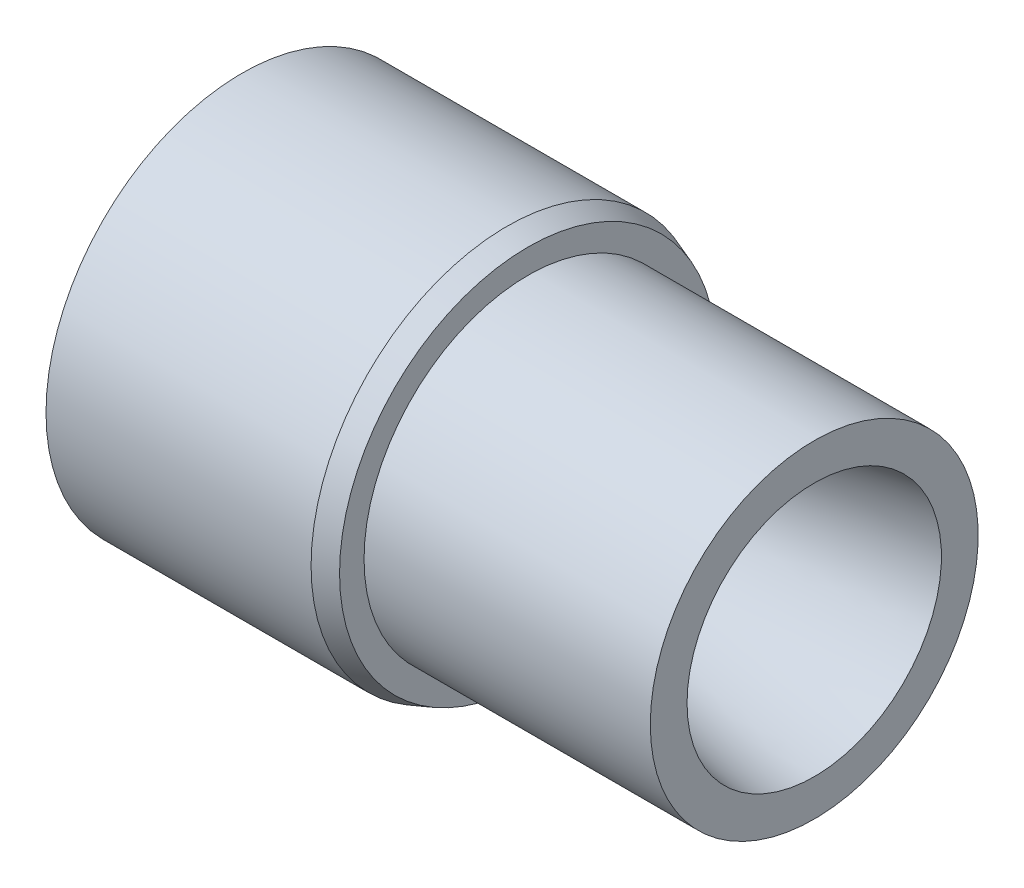
SolidWorks part; units mm, degrees
ref_plane "Front Plane" through (0, 0, 0) normal (0, 0, 1) x (1, 0, 0)
ref_plane "Top Plane" through (0, 0, 0) normal (0, 1, 0) x (1, 0, 0)
ref_plane "Right Plane" through (0, 0, 0) normal (1, 0, 0) x (0, 0, -1)
sketch "Sketch1" plane through (0, 0, 0) normal (0, 0, 1) x (1, 0, 0)
  line L0 (0, 0) -> (176.8872, 0) construction
  line L1 (0, 41.295) -> (27.5254, 41.295) construction
  line L2 (54.4274, 15.285) -> (96.5346, 15.285) construction
  line L3 (42.9453, 29.8255) -> (62.8124, 18.3553)
  line L7 (0, 41.295) -> (0, 50.82)
  line L11 (75.9338, 15.5588) -> (94.1128, 21.868) construction
  line L13 (148.34, 32.975) -> (123.4215, 29.4729) construction
  line L14 (148.34, 32.975) -> (148.34, 42.5)
  line L15 (148.34, 42.5) -> (74.13, 42.5)
  line L16 (74.13, 42.5) -> (74.13, 48.85)
  line L17 (74.13, 48.85) -> (68.7175, 50.82)
  line L18 (68.7175, 50.82) -> (0, 50.82)
  arc A0 (0, 41.295) -> (42.9453, 29.8255) centre (0.1403, -44.3149) cw
  arc A1 (74.13, 15.285) -> (62.8124, 18.3553) centre (74.2724, 38.2046) cw
  arc A2 (74.13, 15.285) -> (75.9338, 15.5588) centre (74.1663, 21.1249) ccw
  spline S0 degree 3 poles (75.9338, 15.5588) (97.1242, 22.9132) (126.0123, 29.837) (148.34, 32.975) knots 0 0 0 0 1 1 1 1
  dimension "D4" = 22.92
  dimension "D5" = 74.13
  dimension "D7" = 5.84
  dimension "D11" = 9.525
  dimension "D6" = 30
  dimension "D3" = 85.61
  dimension "D9" = 74.21
  dimension "D15" = 6.35
  dimension "D1" = 41.295
  dimension "D2" = 15.285
  dimension "D8" = 19.14
  dimension "D10" = 32.975
  dimension "D12" = 8
  dimension "D13" = 9.525
  dimension "D14" = 20
revolve "Revolve1" add sketch "Sketch1" angle 360 about L0
